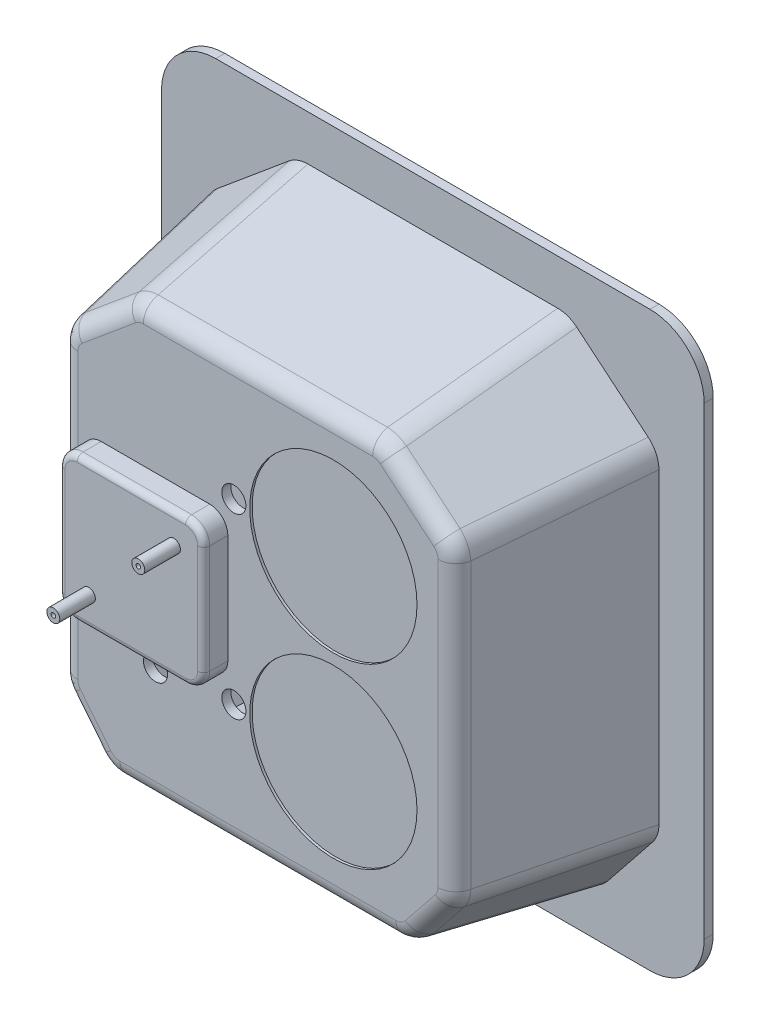
SolidWorks part; units mm, degrees
ref_plane "Front Plane" through (0, 0, 0) normal (0, 0, 1) x (1, 0, 0)
ref_plane "Top Plane" through (0, 0, 0) normal (0, 1, 0) x (1, 0, 0)
ref_plane "Right Plane" through (0, 0, 0) normal (1, 0, 0) x (0, 0, -1)
sketch "SK_Brim_180x190" plane through (0, 0, 0) normal (0, 0, 1) x (1, 0, 0)
  line L1 (-90, -95) -> (90, -95)
  line L2 (-90, -95) -> (-90, 95)
  line L3 (-90, 95) -> (90, 95)
  line L4 (90, -95) -> (90, 95)
  line L5 (-72, -77) -> (72, -77)
  line L6 (-72, -77) -> (-72, 77)
  line L7 (-72, 77) -> (72, 77)
  line L8 (72, -77) -> (72, 77)
extrude "Board_Mount_Brim_3mm" add sketch "SK_Brim_180x190" along normal blind 3
fillet "Brim_Outer_R18" radius 18 4 edges at (-90, 95, 1.5) (90, 95, 1.5) (90, -95, 1.5) (-90, -95, 1.5)
fillet "Brim_Inner_R10" radius 10 4 edges at (-72, 77, 1.5) (72, 77, 1.5) (72, -77, 1.5) (-72, -77, 1.5)
sketch "SK_Cockpit_Octagon" plane through (0, 0, 3) normal (0, 0, 1) x (1, 0, 0)
  line L0 (-55, -80) -> (55, -80)
  line L1 (55, -80) -> (75, -55)
  line L2 (75, -55) -> (75, 55)
  line L3 (75, 55) -> (45, 80)
  line L4 (45, 80) -> (-45, 80)
  line L5 (-45, 80) -> (-75, 55)
  line L6 (-75, 55) -> (-75, -55)
  line L7 (-75, -55) -> (-55, -80)
extrude "Cockpit_Canopy_Draft10deg" add sketch "SK_Cockpit_Octagon" along normal blind 58 draft 10
fillet "Canopy_Corners_R10" radius 10 8 edges at (-69.8865, -53.2063, 32) (-69.8865, 52.605, 32) (-43.1487, 74.8865, 32) (43.1487, 74.8865, 32) (69.8865, 52.605, 32) (69.8865, -53.2063, 32) (52.5423, -74.8865, 32) (-52.5423, -74.8865, 32)
fillet "Canopy_Roof_R6" radius 6 16 edges at (-57.8283, -60.0936, 61) (0, -69.773, 61) (57.8283, -60.0936, 61) (64.773, -1.1804, 61) (52.633, 60.3267, 61) (0, 69.773, 61) (-52.633, 60.3267, 61) (-64.773, -1.1804, 61) (-49.6183, -68.8027, 61) (49.6183, -68.8027, 61) (64.2184, -51.218, 61) (63.8447, 49.7752, 61) (41.0846, 69.1854, 61) (-41.0846, 69.1854, 61) (-63.8447, 49.7752, 61) (-64.2184, -51.218, 61)
sketch "SK_Symmetric_Cavity" plane through (0, 0, 0) normal (0, 0, -1) x (-1, 0, 0)
  line L0 (-53, -77) -> (53, -77)
  line L1 (57.3444, -77) -> (-57.3444, -77) construction
  line L2 (53, -77) -> (72, -52)
  line L3 (72, 57.4649) -> (72, -58.75) construction
  line L4 (72, -52) -> (72, 52)
  line L5 (72, 52) -> (43, 77)
  line L6 (-62, 77) -> (62, 77) construction
  line L7 (43, 77) -> (-43, 77)
  line L8 (-43, 77) -> (-72, 52)
  line L9 (-72, -67) -> (-72, 67) construction
  line L10 (-72, 52) -> (-72, -52)
  line L11 (-72, -52) -> (-53, -77)
extrude "Symmetric_Electronics_Cavity_58H" cut sketch "SK_Symmetric_Cavity" against normal blind 58 draft 10
sketch "Sketch1" plane through (0, 0, 0) normal (0, 0, 1) x (1, 0, 0)
  line L1 (-72, -77) -> (72, -77)
  line L2 (-72, -77) -> (-72, 77)
  line L3 (-72, 77) -> (72, 77)
  line L4 (72, -77) -> (72, 77)
extrude "Boss-Extrude1" add sketch "Sketch1" along normal blind 3
sketch "Sketch2" plane through (0, 0, 3) normal (0, 0, 1) x (1, 0, 0)
  circle A0 centre (0, 0) radius 10
  circle A1 centre (-18.75, -18.75) radius 2.25
  circle A2 centre (-18.75, 18.75) radius 2.25
  circle A3 centre (18.75, -18.75) radius 2.25
  circle A4 centre (18.75, 18.75) radius 2.25
extrude "Cut-Extrude1" cut sketch "Sketch2" against normal blind 3.2
sketch "Sketch3" plane through (0, 0, 3) normal (0, 0, 1) x (1, 0, 0)
  circle A0 centre (-18.75, -18.75) radius 4.5
  circle A1 centre (-18.75, 18.75) radius 4.5
  circle A2 centre (18.75, -18.75) radius 4.5
  circle A3 centre (18.75, 18.75) radius 4.5
extrude "Cut-Extrude2" cut sketch "Sketch3" against normal blind 1.5
sketch "Sketch7" plane through (0, 0, 61) normal (0, 0, 1) x (1, 0, 0)
  circle A0 centre (25, -29.5) radius 28.5
  circle A1 centre (25, 29.5) radius 28.5
extrude "Boss-Extrude4" add sketch "Sketch7" along normal blind 1.5
sketch "Sketch8" plane through (0, 0, 62.5) normal (0, 0, 1) x (1, 0, 0)
  circle A0 centre (25, -29.5) radius 28.5
  circle A1 centre (25, 29.5) radius 28.5
extrude "Cut-Extrude4" cut sketch "Sketch8" against normal blind 1.5
sketch "Sketch12" plane through (0, 0, 61) normal (0, 0, 1) x (1, 0, 0)
  circle A0 centre (25, -29.5) radius 27.75
extrude "Cut-Extrude8" cut sketch "Sketch12" against normal blind 0.8
sketch "Sketch13" plane through (0, 0, 61) normal (0, 0, 1) x (1, 0, 0)
  circle A0 centre (25, 29.5) radius 27.75
extrude "Cut-Extrude9" cut sketch "Sketch13" against normal blind 0.8
sketch "Sketch14" plane through (0, 0, 61) normal (0, 0, 1) x (1, 0, 0)
  line L1 (-58, -24) -> (-10, -24)
  line L2 (-58, -24) -> (-58, 24)
  line L3 (-58, 24) -> (-10, 24)
  line L4 (-10, -24) -> (-10, 24)
extrude "Boss-Extrude5" add sketch "Sketch14" along normal blind 8
fillet "Fillet3" radius 6 4 edges at (-58, 24, 65) (-10, 24, 65) (-10, -24, 65) (-58, -24, 65)
fillet "Fillet4" radius 2 8 edges at (-58, 0, 69) (-34, -24, 69) (-10, 0, 69) (-34, 24, 69) (-56.2426, -22.2426, 69) (-11.7574, -22.2426, 69) (-11.7574, 22.2426, 69) (-56.2426, 22.2426, 69)
sketch "Sketch15" plane through (0, 0, 69) normal (0, 0, 1) x (1, 0, 0)
  circle A0 centre (-48.1, -14.1) radius 2.15
  circle A1 centre (-19.9, 14.1) radius 2.15
extrude "Boss-Extrude6" add sketch "Sketch15" along normal blind 11.8
sketch "Sketch16" plane through (0, 0, 80.8) normal (0, 0, 1) x (1, 0, 0)
  circle A0 centre (-48.1, -14.1) radius 0.75
  circle A1 centre (-19.9, 14.1) radius 0.75
extrude "Cut-Extrude10" cut sketch "Sketch16" against normal blind 11.3
sketch "Sketch17" plane through (0, 0, 61) normal (0, 0, 1) x (1, 0, 0)
  circle A0 centre (-8, -29.5) radius 4
  circle A1 centre (-8, 29.5) radius 4
extrude "Cut-Extrude11" cut sketch "Sketch17" against normal blind 4
sketch "Sketch18" plane through (0, 0, 61) normal (0, 0, 1) x (1, 0, 0)
  circle A0 centre (-34, -32) radius 4
extrude "Cut-Extrude12" cut sketch "Sketch18" against normal blind 4
